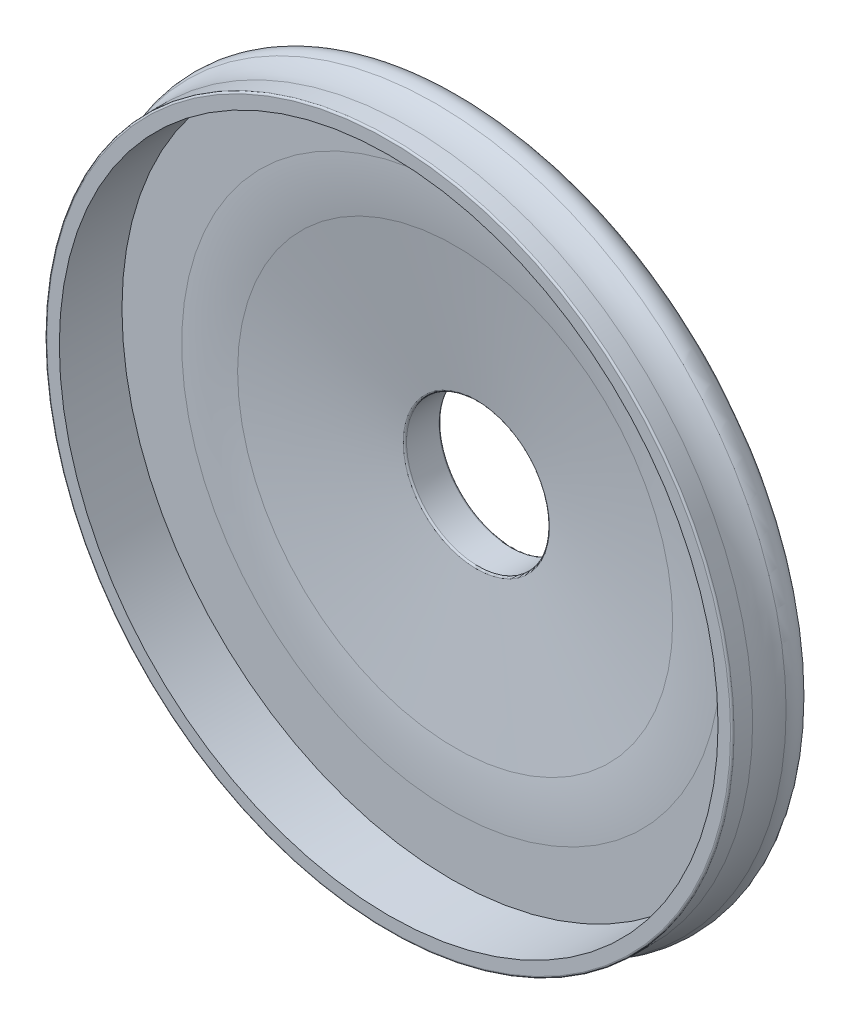
SolidWorks part; units mm, degrees
material "Phosphor bronze 10% D, UNS C52400"
ref_plane "Front Plane" through (0, 0, 0) normal (1, 0, 0) x (0, 1, 0)
ref_plane "Top Plane" through (0, 0, 0) normal (0, 0, 1) x (0, 1, 0)
ref_plane "Right Plane" through (0, 0, 0) normal (0, 1, 0) x (-1, 0, 0)
sketch "Sketch1" plane through (0, 0, 0) normal (0, 0, 1) x (0, 1, 0)
  circle A0 centre (0, 0) radius 9.2
extrude "Extrude-Thin1" add sketch "Sketch1" along normal blind 1.5 thin
sketch "Sketch4" plane through (0, 0, 0) normal (1, 0, 0) x (0, 1, 0)
  line L0 (-9.6, 0) -> (9.6, 0) construction
  line L1 (0, -1.25) -> (0, -2)
  line L2 (8.5, 0) -> (9.9, 0)
  line L3 (0, 0) -> (0, 2) construction
  line L5 (0, 0) -> (0, -1.25) construction
  line L6 (0, -1.25) -> (8.5, 0)
  ellipse E0 centre (0, 0) end of major axis (9.9, 0) minor radius 2 (0, -2) -> (9.9, 0) ccw
revolve "Revolve1" add sketch "Sketch4" angle 360 about L5
sketch "Sketch5" plane through (0, 0, 1.5) normal (0, 0, 1) x (1, 0, 0)
  circle A0 centre (0, 0) radius 2
extrude "Cut-Extrude1" cut sketch "Sketch5" against normal blind 10
fillet "Fillet1" radius 1.6 1 edges at (-9.6, 0, 0)
sketch "Sketch6" plane through (0, 0, 0) normal (0, 0, 1) x (0, 1, 0)
  circle A0 centre (0, 0) radius 9.2
extrude "Cut-Extrude2" cut sketch "Sketch6" against normal blind 0.25
fillet "Fillet3" radius 10 1 edges at (6.8, 0, -0.25)
fillet "Fillet4" radius 0.5 1 edges at (9.9, 0, 0)
fillet "Fillet5" radius 0.05 2 edges at (2, 0, -1.9588) (2, 0, -0.9559)
fillet "Fillet6" radius 0.05 1 edges at (0, 9.6, 1.5)
